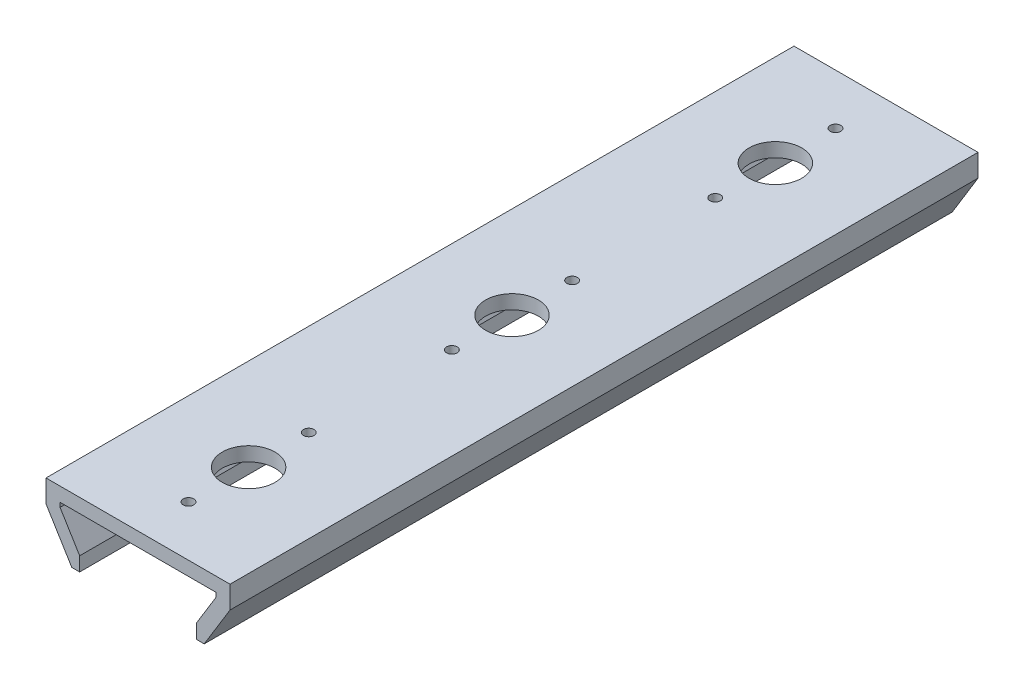
SolidWorks part; units mm, degrees
ref_plane "Płaszczyzna przednia" through (0, 0, 0) normal (0, 0, 1) x (1, 0, 0)
ref_plane "Płaszczyzna górna" through (0, 0, 0) normal (0, 1, 0) x (1, 0, 0)
ref_plane "Płaszczyzna prawa" through (0, 0, 0) normal (1, 0, 0) x (0, 0, -1)
sketch "Sketch1" plane through (0, 0, 0) normal (0, 0, 1) x (1, 0, 0)
  line L0 (0, -13.2894) -> (0, -81.2091) construction
  line L1 (0, -13.4894) -> (22, -13.4894)
  line L2 (22, -13.4894) -> (22, -14.4894)
  line L3 (16.5, -23.4894) -> (0, -23.4894)
  line L4 (22, -14.4894) -> (16.5, -23.4894)
  line L5 (0, -13.4894) -> (0, -23.4894)
  line L6 (0, -13.2894) -> (22.2, -13.2894)
  line L7 (22.2, -13.2894) -> (22.2, -14.5456)
  line L8 (22.2, -14.5456) -> (16.6122, -23.6894)
  line L9 (16.6122, -23.6894) -> (0, -23.6894)
  line L11 (18.8555, -27.6894) -> (16.6122, -27.6894)
  line L13 (-26.2, -9.2894) -> (26.2, -9.2894)
  line L14 (26.2, -9.2894) -> (26.2, -15.6711)
  line L15 (26.2, -15.6711) -> (18.8555, -27.6894)
  line L16 (0, -13.2894) -> (0, -31.461)
  line L17 (16.6122, -23.6894) -> (16.6122, -27.6894)
  line L18 (-4.2, -9.2894) -> (-4.2, -27.6894) construction
  line L20 (-4.2, -9.2894) -> (26.2, -9.2894) construction
  line L21 (18.8555, -27.6894) -> (-4.2, -27.6894) construction
  line L22 (-0.2, -13.2894) -> (-0.2, -23.6894) construction
  line L23 (16.6122, -23.6894) -> (-0.2, -23.6894) construction
  line L24 (-0.2, -13.2894) -> (22.2, -13.2894) construction
  line L25 (-26.2, -9.2894) -> (-26.2, -15.6711)
  line L26 (-26.2, -15.6711) -> (-18.8555, -27.6894)
  line L27 (-18.8555, -27.6894) -> (-16.6122, -27.6894)
  line L28 (-16.6122, -23.6894) -> (-16.6122, -27.6894)
  line L29 (-22.2, -14.5456) -> (-16.6122, -23.6894)
  line L30 (-22.2, -13.2894) -> (-22.2, -14.5456)
  line L31 (0, -13.2894) -> (-22.2, -13.2894)
  point P4 (22, -23.4894)
  dimension "D1" = 9
  dimension "D2" = 5.5
  dimension "D3" = 10
  dimension "D4" = 22
  dimension "D5" = 0.2
  dimension "D6" = 4
extrude "Boss-Extrude1" add sketch "Sketch1" along normal blind 213 contours L31 L6 L7 L8 L17 L11 L15 L14 L13 L25 L26 L27 L28 L29 L30 region at (-11.1, -12.734, 0)
sketch "Sketch2" plane through (0, -9.2894, 0) normal (0, 1, 0) x (1, 0, 0)
  line L0 (0, 0) -> (0, -186.0262) construction
  circle A0 centre (0, -31.5) radius 7.5
  circle A1 centre (0, -106.5) radius 7.5
  circle A2 centre (0, -181.5) radius 7.5
  dimension "D2" = 15
  dimension "D1" = 186.0262
  dimension "D3" = 31.5
  dimension "D5" = 75
  dimension "D4" = 3
extrude "Cut-Extrude1" cut sketch "Sketch2" against normal blind 213
sketch "Sketch7" plane through (0, -9.2894, 0) normal (0, 1, 0) x (1, 0, 0)
  line L0 (0, -160.3757) -> (0, -189.9157) construction
  line L1 (-0.5, -160.3757) -> (0.5, -160.3757)
  line L2 (-4.5, -164.3757) -> (-4.5, -170.3757)
  line L3 (-4.5, -170.3757) -> (4.5, -170.3757)
  line L4 (4.5, -164.3757) -> (4.5, -170.3757)
  line L5 (-4.5, -160.3757) -> (4.5, -170.3757) construction
  line L6 (-4.5, -170.3757) -> (4.5, -160.3757) construction
  line L7 (-81.2349, -181.5) -> (81.2349, -181.5) construction
  circle A0 centre (0, -181.5) radius 12
  circle A1 centre (0, -181.5) radius 7.5 construction
  circle A2 centre (0, -164.3757) radius 1.5
  arc A3 (0.5, -160.3757) -> (4.5, -164.3757) centre (0.5, -164.3757) cw
  arc A4 (-0.5, -160.3757) -> (-4.5, -164.3757) centre (-0.5, -164.3757) ccw
  circle A5 centre (0, -198.6243) radius 1.5
  point P4 (-80.2434, -146.7844)
  dimension "D1" = 24
  dimension "D4" = 3
  dimension "D6" = 4
  dimension "D2" = 10
  dimension "D3" = 9
  dimension "D5" = 4
extrude "Cut-Extrude2" cut sketch "Sketch7" against normal blind 10 contours A5 | A2 region at (0, -9.2894, 198.6243)
pattern_linear "LPattern1" count 3 spacing 75 along (0, 0, -1) of "Cut-Extrude2"
sketch "Sketch3" plane through (0, -9.2894, 0) normal (0, 1, 0) x (1, 0, 0)
  line L0 (-5, -36.5) -> (5, -26.5) construction
  line L1 (-5, -26.5) -> (5, -26.5)
  line L2 (-5, -26.5) -> (-5, -36.5)
  line L3 (-5, -36.5) -> (5, -36.5)
  line L4 (5, -26.5) -> (5, -36.5)
  circle A0 centre (0, -31.5) radius 7.5
  circle A1 centre (0, -31.5) radius 7.5 construction
  dimension "D1" = 10
  dimension "D2" = 10
ref_plane "Plane1" through (0, 0.7106, 0) normal (0, 1, 0) x (1, 0, 0)
sketch "Sketch5" plane through (0, 0.7106, 0) normal (0, 1, 0) x (1, 0, 0)
  line L1 (-5, -26.5) -> (5, -26.5)
  line L2 (-5, -26.5) -> (-5, -36.5)
  line L3 (-5, -36.5) -> (5, -36.5)
  line L4 (5, -26.5) -> (5, -36.5)
  dimension "D1" = 10
  dimension "D2" = 10
